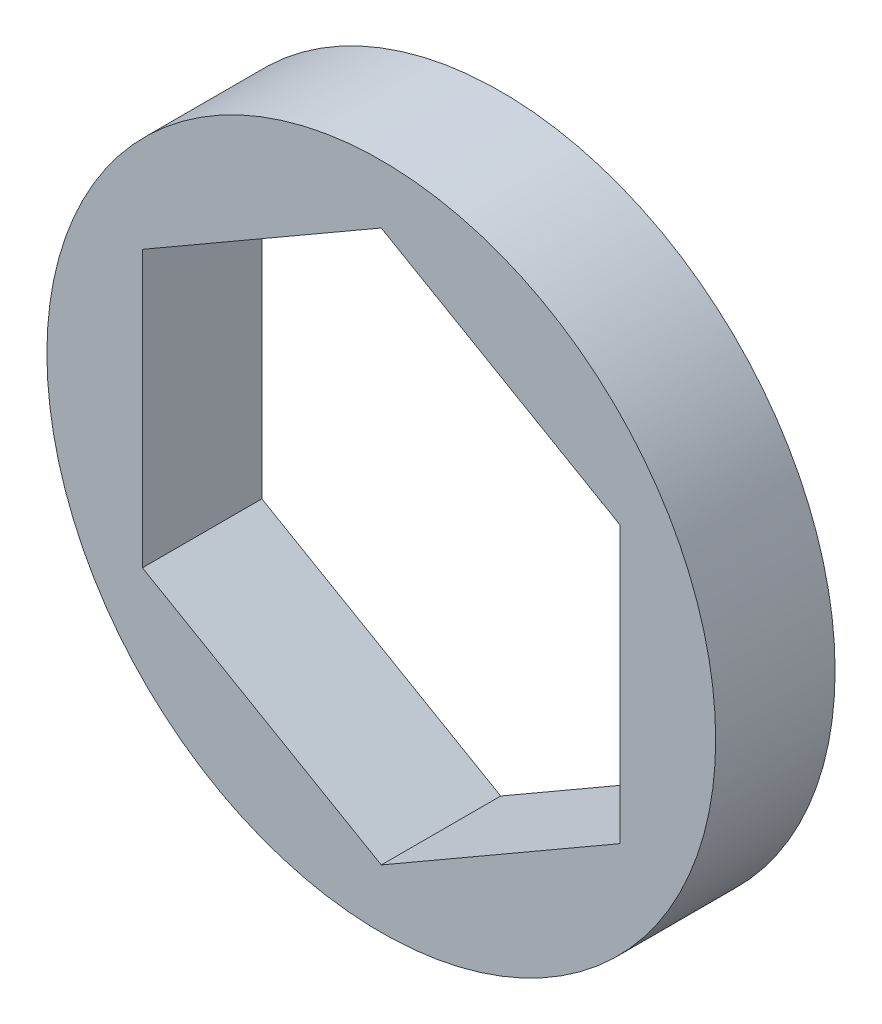
SolidWorks part; units mm, degrees
material "PET"
ref_plane "Front Plane" through (0, 0, 0) normal (0, 0, 1) x (1, 0, 0)
ref_plane "Top Plane" through (0, 0, 0) normal (0, 1, 0) x (1, 0, 0)
ref_plane "Right Plane" through (0, 0, 0) normal (1, 0, 0) x (0, 0, -1)
sketch "Sketch1" plane through (0, 0, 0) normal (0, 0, 1) x (1, 0, 0)
  line L1 (0, 7.3323) -> (-6.35, 3.6662)
  line L2 (-6.35, 3.6662) -> (-6.35, -3.6662)
  line L3 (-6.35, -3.6662) -> (0, -7.3323)
  line L4 (0, -7.3323) -> (6.35, -3.6662)
  line L5 (6.35, -3.6662) -> (6.35, 3.6662)
  line L6 (6.35, 3.6662) -> (0, 7.3323)
  circle A0 centre (0, 0) radius 6.35 construction
  circle A1 centre (0, 0) radius 8.89
  dimension "D1" = 12.7
  dimension "D2" = 17.78
extrude "Boss-Extrude1" add sketch "Sketch1" along normal mid plane 3.175
